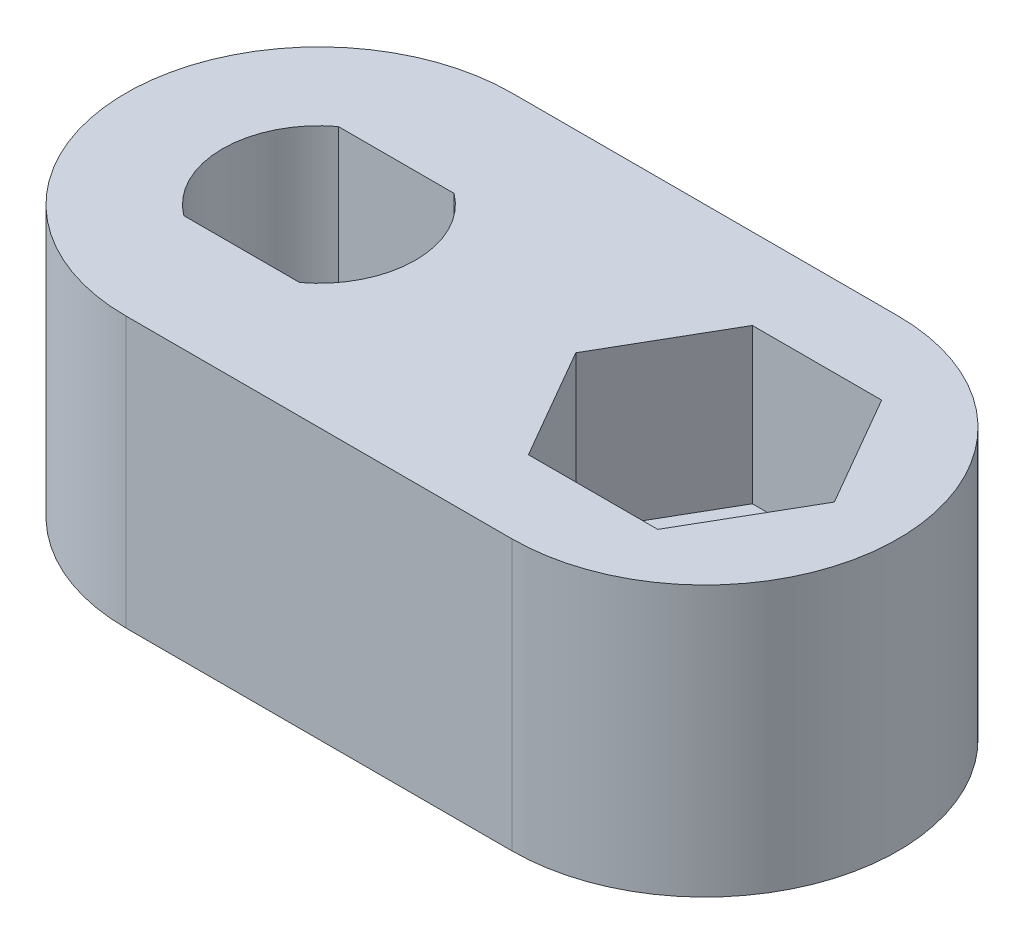
SolidWorks part; units mm, degrees
ref_plane "Front Plane" through (0, 0, 0) normal (0, 0, 1) x (1, 0, 0)
ref_plane "Top Plane" through (0, 0, 0) normal (0, 1, 0) x (1, 0, 0)
ref_plane "Right Plane" through (0, 0, 0) normal (1, 0, 0) x (0, 0, -1)
sketch "Sketch1" plane through (0, 0, 0) normal (0, 1, 0) x (1, 0, 0)
  line L0 (0, 0) -> (10, 0) construction
  line L1 (0, 5) -> (10, 5)
  line L2 (0, -5) -> (10, -5)
  arc A0 (0, 5) -> (0, -5) centre (0, 0) ccw
  arc A1 (10, -5) -> (10, 5) centre (10, 0) ccw
  point P3 (5, 0)
  dimension "D1" = 10
  dimension "D2" = 10
extrude "Boss-Extrude1" add sketch "Sketch1" along normal blind 7
sketch "Sketch2" plane through (0, 7, 0) normal (0, 1, 0) x (1, 0, 0)
  line L0 (-1.5, -2) -> (1.5, -2)
  line L1 (-1.5, 2) -> (1.5, 2)
  line L2 (0, 0) -> (-3.1448, 0) construction
  circle A0 centre (0, 0) radius 2.5
  dimension "D2" = 5
  dimension "D1" = 4
extrude "Cut-Extrude1" cut sketch "Sketch2" against normal blind 4 contours L0 A0 L1 region at (0, 7, 0)
hole_wizard "CSK for M3 Hex Socket Countersunk Cap Screw2" positions "Sketch8" profile "Sketch7" countersink size "M3" standard "ISO"
sketch "Sketch8" plane through (0, 0, 0) normal (0, -1, 0) x (-1, 0, 0)
  point P0 (0, 0)
sketch "Sketch7" plane through (0, 0, 0) normal (1, 0, 0) x (0, 0, -1)
  line L0 (0, 0) -> (0, 8.5215)
  line L1 (0, 8.5215) -> (1.7, 7.5)
  line L2 (1.7, 7.5) -> (1.7, 1.66)
  line L3 (1.7, 1.66) -> (3.36, 0)
  line L5 (3.36, 0) -> (0, 0)
  line L6 (-1.7, 1.66) -> (-3.36, 0) construction
  line L10 (0, 8.5215) -> (-1.7, 7.5) construction
  line L11 (0, -6.35) -> (0, 107.95) construction
  dimension "Hole Dia." = 3.4
  dimension "Hole Depth" = 7.5
  dimension "Near C'Sink Dia." = 6.72
  dimension "Near C'Sink Angle" = 90
  dimension "Drill Angle" = 118
hole_wizard "Hole1" positions "Sketch9" profile "Sketch10" legacy end condition through all
sketch "Sketch9" plane through (0, 0, 0) normal (0, -1, 0) x (-1, 0, 0)
  point P0 (-10, 0)
sketch "Sketch10" plane through (10, 0, 0) normal (1, 0, 0) x (0, 0, -1)
  line L0 (0, 0) -> (0, 7)
  line L1 (0, 7) -> (2.075, 7)
  line L2 (2.075, 7) -> (2.075, 0)
  line L3 (2.075, 0) -> (0, 0)
  line L4 (0, 110) -> (0, -10) construction
  dimension "Diameter" = 4.15
  dimension "Depth" = 7
sketch "Sketch11" plane through (0, 7, 0) normal (0, 1, 0) x (1, 0, 0)
  line L0 (10, 5) -> (0, 5) construction
  line L1 (13.3486, 0) -> (11.6743, 2.9)
  line L2 (11.6743, 2.9) -> (8.3257, 2.9)
  line L3 (8.3257, 2.9) -> (6.6514, 0)
  line L4 (6.6514, 0) -> (8.3257, -2.9)
  line L5 (8.3257, -2.9) -> (11.6743, -2.9)
  line L6 (11.6743, -2.9) -> (13.3486, 0)
  circle A0 centre (10, 0) radius 2.9 construction
  dimension "D1" = 5.8
extrude "Cut-Extrude2" cut sketch "Sketch11" against normal blind 4
